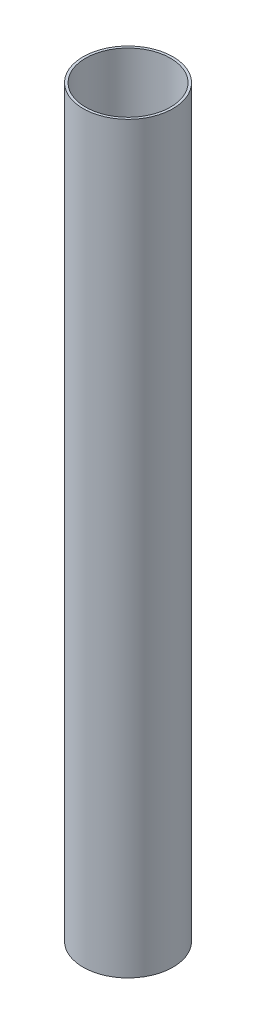
SolidWorks part; units mm, degrees
ref_plane "Front Plane" through (0, 0, 0) normal (0, 0, 1) x (1, 0, 0)
ref_plane "Top Plane" through (0, 0, 0) normal (0, 1, 0) x (1, 0, 0)
ref_plane "Right Plane" through (0, 0, 0) normal (1, 0, 0) x (0, 0, -1)
sketch "Sketch1" plane through (0, 0, 0) normal (0, 0, 1) x (1, 0, 0)
  line L0 (0, 0) -> (0, 304.8) construction
  line L1 (-15.35, 0) -> (-14.5, 0)
  line L2 (-15.35, 0) -> (-15.35, 254)
  line L3 (-15.35, 254) -> (-14.5, 254)
  line L4 (15.35, 0) -> (15.35, 254)
  line L5 (-14.5, 0) -> (-14.5, 254)
  line L6 (14.5, 254) -> (14.5, 0)
  line L7 (14.5, 0) -> (15.35, 0)
  line L8 (14.5, 254) -> (15.35, 254)
  dimension "D1" = 30.7
  dimension "12" = 254
  dimension "D2" = 29
revolve "Revolve2" add sketch "Sketch1" angle 360 about L0 region at (-14.925, 127, 0)
